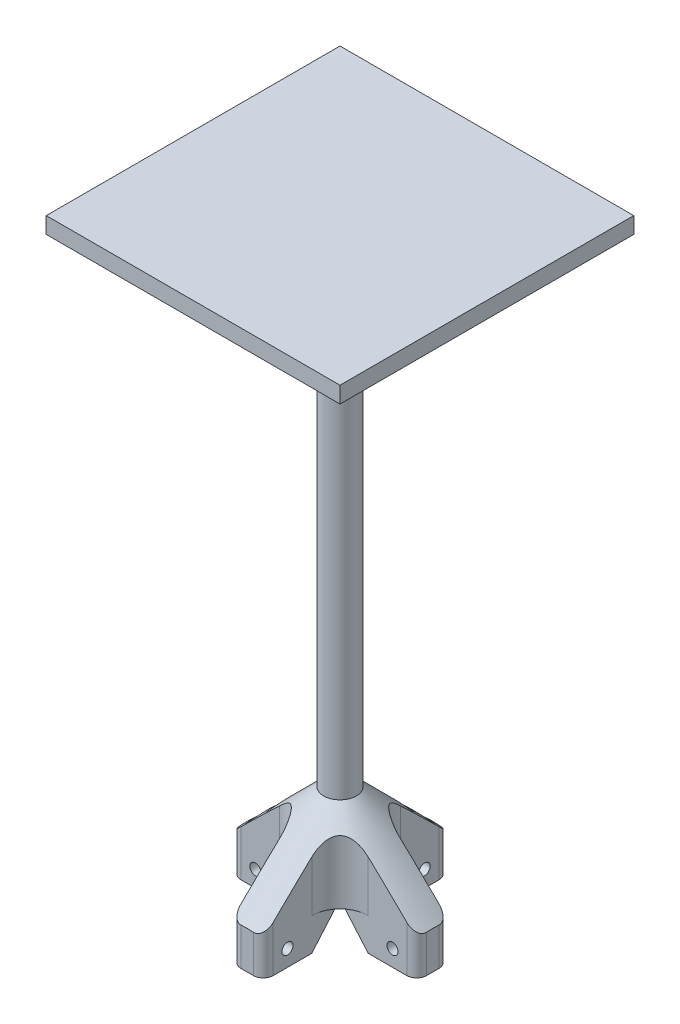
SolidWorks part; units mm, degrees
ref_plane "Front Plane" through (0, 0, 0) normal (0, 0, 1) x (1, 0, 0)
ref_plane "Top Plane" through (0, 0, 0) normal (0, 1, 0) x (1, 0, 0)
ref_plane "Right Plane" through (0, 0, 0) normal (1, 0, 0) x (0, 0, -1)
sketch "Sketch8" plane through (0, 0, 0) normal (0, 1, 0) x (1, 0, 0)
  line L0 (13.575, 4.925) -> (28.425, 4.925)
  line L1 (-4.925, 13.575) -> (4.925, 13.575)
  line L2 (-4.925, 13.575) -> (-4.925, 28.425)
  line L3 (-4.925, 28.425) -> (4.925, 28.425)
  line L4 (4.925, 13.575) -> (4.925, 28.425)
  line L5 (-4.925, 13.575) -> (4.925, 28.425) construction
  line L6 (-4.925, 28.425) -> (4.925, 13.575) construction
  line L7 (13.575, 4.925) -> (13.575, -4.925)
  line L8 (13.575, -4.925) -> (28.425, -4.925)
  line L9 (28.425, 4.925) -> (28.425, -4.925)
  line L10 (4.925, -13.575) -> (4.925, -28.425)
  line L11 (4.925, -13.575) -> (-4.925, -13.575)
  line L12 (-4.925, -13.575) -> (-4.925, -28.425)
  line L13 (4.925, -28.425) -> (-4.925, -28.425)
  line L14 (-13.575, -4.925) -> (-28.425, -4.925)
  line L15 (-13.575, -4.925) -> (-13.575, 4.925)
  line L16 (-13.575, 4.925) -> (-28.425, 4.925)
  line L17 (-28.425, -4.925) -> (-28.425, 4.925)
  line L18 (-13.575, 4.925) -> (0, 4.925)
  line L19 (-13.575, -4.925) -> (0, -4.925)
  line L20 (4.925, 13.575) -> (4.925, 0)
  line L21 (-4.925, 13.575) -> (-4.925, 0)
  line L22 (13.575, -4.925) -> (0, -4.925)
  line L23 (13.575, 4.925) -> (0, 4.925)
  line L24 (-4.925, -13.575) -> (-4.925, 0)
  line L25 (4.925, -13.575) -> (4.925, 0)
  point P0 (0, 21)
  point P21 (0, 0)
  point P38 (0, 0)
  dimension "D1" = 21
  dimension "D2" = 9.85
  dimension "D3" = 4
  dimension "D5" = 14.85
  dimension "D4" = 4
extrude "Boss-Extrude4" add sketch "Sketch8" along normal blind 1.5 separate body contours L17 L14 L15 L16 | L1 L4 L3 L2 | L9 L0 L7 L8 | L13 L10 L11 L12 | L19 L24 L21 L18 L15 | L23 L20 L1 L21 L18 | L25 L22 L7 L23 L20 | L11 L25 L22 L19 L24 | L24 L19 | L18 L21 | L20 L23 | L22 L25 region at (21, 0, 0) region at (9.25, 0, 0) region at (0, 0, -9.25) region at (0, 0, 0) region at (0, 0, 9.25) region at (0, 0, -21) region at (0, 0, 21) region at (-9.25, 0, 0) region at (-21, 0, 0)
sketch "Sketch7" plane through (0, 1.5, 0) normal (0, 1, 0) x (1, 0, 0)
  circle A0 centre (0, 0) radius 5
  dimension "D1" = 10
extrude "Boss-Extrude3" add sketch "Sketch7" along normal blind 170
fillet "Fillet3" radius 8.65 4 edges at (4.925, 0.75, -4.925) (4.925, 0.75, 4.925) (-4.925, 0.75, 4.925) (-4.925, 0.75, -4.925)
sketch "Sketch13" plane through (0, 0, 0) normal (0, -1, 0) x (1, 0, 0)
  line L0 (-4.925, -28.425) -> (-4.925, -13.575) construction
  line L1 (-4.925, -28.425) -> (4.925, -28.425) construction
  line L2 (-4.925, -28.425) -> (-4.925, -13.575)
  line L3 (-4.925, -28.425) -> (4.925, -28.425)
  line L4 (4.925, -28.425) -> (4.925, -13.575) construction
  line L5 (-4.925, -28.425) -> (4.925, -28.425)
  line L6 (-4.925, -28.425) -> (-4.925, -13.575)
  line L7 (-4.925, -13.575) -> (4.925, -13.575)
  line L8 (4.925, -28.425) -> (4.925, -13.575)
  line L9 (-28.425, 4.925) -> (-13.575, 4.925)
  line L10 (-28.425, 4.925) -> (-28.425, -4.925)
  line L11 (-28.425, -4.925) -> (-13.575, -4.925)
  line L12 (-13.575, 4.925) -> (-13.575, -4.925)
  line L13 (4.925, 28.425) -> (4.925, 13.575)
  line L14 (4.925, 28.425) -> (-4.925, 28.425)
  line L15 (-4.925, 28.425) -> (-4.925, 13.575)
  line L16 (4.925, 13.575) -> (-4.925, 13.575)
  line L17 (28.425, -4.925) -> (13.575, -4.925)
  line L18 (28.425, -4.925) -> (28.425, 4.925)
  line L19 (28.425, 4.925) -> (13.575, 4.925)
  line L20 (13.575, -4.925) -> (13.575, 4.925)
  point P21 (0, 0)
  line M10 (-28.425, 4.925) -> (-28.425, -4.925)
  line M11 (-28.425, -4.925) -> (-13.575, -4.925)
  line M14 (-4.925, -28.425) -> (4.925, -28.425)
  line M15 (4.925, -28.425) -> (4.925, -13.575)
  line M17 (13.575, -4.925) -> (28.425, -4.925)
  line M18 (28.425, -4.925) -> (28.425, 4.925)
  line M19 (28.425, 4.925) -> (13.575, 4.925)
  line M21 (4.925, 13.575) -> (4.925, 28.425)
  line M22 (4.925, 28.425) -> (-4.925, 28.425)
  line M23 (-4.925, 28.425) -> (-4.925, 13.575)
  line M25 (-13.575, 4.925) -> (-28.425, 4.925)
  dimension "D1" = 14.85
  dimension "D2" = 4
extrude "Boss-Extrude7" add sketch "Sketch13" along normal blind 10 contours L7 L2 M14 M15 | L12 M25 M10 M11 | L16 M21 M22 M23 | L20 M17 M18 M19 region at (0, 0, -21) region at (-21, 0, 0) region at (0, 0, 21) region at (21, 0, 0)
hole_wizard "M3 Clearance Hole2" positions "Sketch9" profile "Sketch10" hole size "M3" standard "ANSI Metric" end condition up to next
sketch "Sketch9" plane through (-4.925, 2.575, 0) normal (1, 0, 0) x (0, -1, 0)
  line L2 (1.075, -4.925) -> (1.075, 4.925) construction
  line L3 (1.075, 5) -> (1.075, -5) construction
  line L4 (1.075, 5) -> (1.075, -5)
  line L7 (12.575, 13.575) -> (2.575, 13.575) construction
  line L8 (12.575, 13.575) -> (2.575, 13.575)
  point P15 (1.075, 0)
  point P38 (7.575, 21)
  point P45 (7.575, 13.575)
  dimension "D1" = 21
sketch "Sketch10" plane through (-4.925, -5, -21) normal (0, 1, 0) x (0, 0, 1)
  line L0 (0, 0) -> (0, 9.851)
  line L1 (0, 9.851) -> (1.7, 9.851)
  line L2 (1.7, 9.851) -> (1.7, 0)
  line L5 (1.7, 0) -> (0, 0)
  line L11 (0, -6.35) -> (0, 107.95) construction
  dimension "Thru Hole Dia." = 3.4
  dimension "Thru Hole Depth" = 9.851
pattern_circular "CirPattern1" count 4 over 360 about axis through (0, 171.5, 0) along (0, -1, 0) of "M3 Clearance Hole2" reverse direction yes
fillet "Fillet8" radius 3 8 edges at (4.925, -4.25, -28.425) (-4.925, -4.25, -28.425) (28.425, -4.25, -4.925) (28.425, -4.25, 4.925) (4.925, -4.25, 28.425) (-4.925, -4.25, 28.425) (-28.425, -4.25, 4.925) (-28.425, -4.25, -4.925)
sketch "Sketch11" plane through (0, 171.5, 0) normal (0, 1, 0) x (1, 0, 0)
  line L1 (-45, 45) -> (45, 45)
  line L2 (-45, 45) -> (-45, -45)
  line L3 (-45, -45) -> (45, -45)
  line L4 (45, 45) -> (45, -45)
  line L5 (-45, 45) -> (45, -45) construction
  line L6 (-45, -45) -> (45, 45) construction
  point P0 (0, 0)
  dimension "D1" = 90
extrude "Boss-Extrude5" add sketch "Sketch11" along normal blind 5
chamfer "Chamfer1" distance 23.5 angle 45 1 edges at (0, 1.5, 5)
fillet "Fillet5" radius 20 1 edges at (0, 171.5, 5)
chamfer "Chamfer2" distance 10 distance2 8.6 4 edges at (13.575, 0, 0) (0, 0, 13.575) (-13.575, 0, 0) (0, 0, -13.575) first distance on face at (13.575, -5, 0) first distance on face at (0, -5, 13.575) first distance on face at (-13.575, -5, 0) first distance on face at (0, -5, -13.575)
